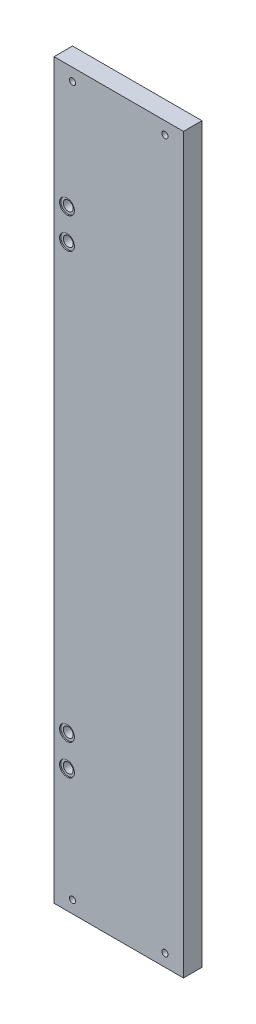
SolidWorks part; units mm, degrees
material "西洋杉"
ref_plane "正面" through (0, 0, 0) normal (0, 0, 1) x (1, 0, 0)
ref_plane "平面" through (0, 0, 0) normal (0, 1, 0) x (1, 0, 0)
ref_plane "右側面" through (0, 0, 0) normal (1, 0, 0) x (0, 0, -1)
sketch "ｽｹｯﾁ1" plane through (0, 0, 0) normal (0, 0, 1) x (1, 0, 0)
  line L1 (-52.5, 297.5) -> (52.5, 297.5)
  line L2 (-52.5, 297.5) -> (-52.5, -297.5)
  line L3 (-52.5, -297.5) -> (52.5, -297.5)
  line L4 (52.5, 297.5) -> (52.5, -297.5)
  line L5 (-52.5, 297.5) -> (52.5, -297.5) construction
  line L6 (-52.5, -297.5) -> (52.5, 297.5) construction
  point P0 (0, 0)
  dimension "D1" = 595
  dimension "D2" = 105
extrude "ﾎﾞｽ - 押し出し1" add sketch "ｽｹｯﾁ1" along normal blind 15
sketch "ｽｹｯﾁ2" plane through (0, 0, 15) normal (0, 0, 1) x (1, 0, 0)
  line L0 (-42, 297.5) -> (-42, -297.5) construction
  line L1 (52.5, 297.5) -> (-52.5, 297.5) construction
  line L2 (-52.5, -297.5) -> (52.5, -297.5) construction
  line L3 (-52.5, 297.5) -> (-52.5, -297.5) construction
  line L4 (-52.5, 287.5) -> (52.5, 287.5) construction
  line L5 (52.5, -297.5) -> (52.5, 297.5) construction
  circle A0 centre (-42, 197.5) radius 4
  circle A6 centre (-37.5, 287.5) radius 2.5
  circle A7 centre (-42, 172.5) radius 4
  dimension "D2" = 8
  dimension "D4" = 5
  dimension "D8" = 8
  dimension "D1" = 10.5
  dimension "D3" = 100
  dimension "D5" = 10
  dimension "D6" = 105
  dimension "D10" = 595
  dimension "D7" = 15
  dimension "D9" = 25
extrude "ｶｯﾄ - 押し出し2" cut sketch "ｽｹｯﾁ2" against normal through all contours A0 | A7
extrude "ｶｯﾄ - 押し出し3" cut sketch "ｽｹｯﾁ2<5>" against normal through all contours A6
sketch "ｽｹｯﾁ2<5>" plane through (0, 0, 15) normal (0, 0, 1) x (1, 0, 0) same geometry as "ｽｹｯﾁ2"
mirror "ﾐﾗｰ1" about plane through (0, 0, 0) normal (0, 1, 0) of "ｶｯﾄ - 押し出し3"
mirror "ﾐﾗｰ2" about plane through (0, 0, 0) normal (0, 1, 0) of "ｶｯﾄ - 押し出し2"
mirror "ﾐﾗｰ3" about plane through (0, 0, 0) normal (1, 0, 0) of "ﾐﾗｰ1"
sketch "ｽｹｯﾁ3" plane through (0, 0, 15) normal (0, 0, 1) x (1, 0, 0)
  circle A0 centre (-42, 197.5) radius 6
  circle A1 centre (-42, 172.5) radius 6
  dimension "D1" = 12
  dimension "D2" = 12
extrude "ｶｯﾄ - 押し出し4" cut sketch "ｽｹｯﾁ3" against normal blind 1
mirror "ﾐﾗｰ4" about plane through (0, 0, 0) normal (0, 1, 0) of "ｶｯﾄ - 押し出し4"
equation "\"D8@ｽｹｯﾁ2\"=\"D2@ｽｹｯﾁ2\""
